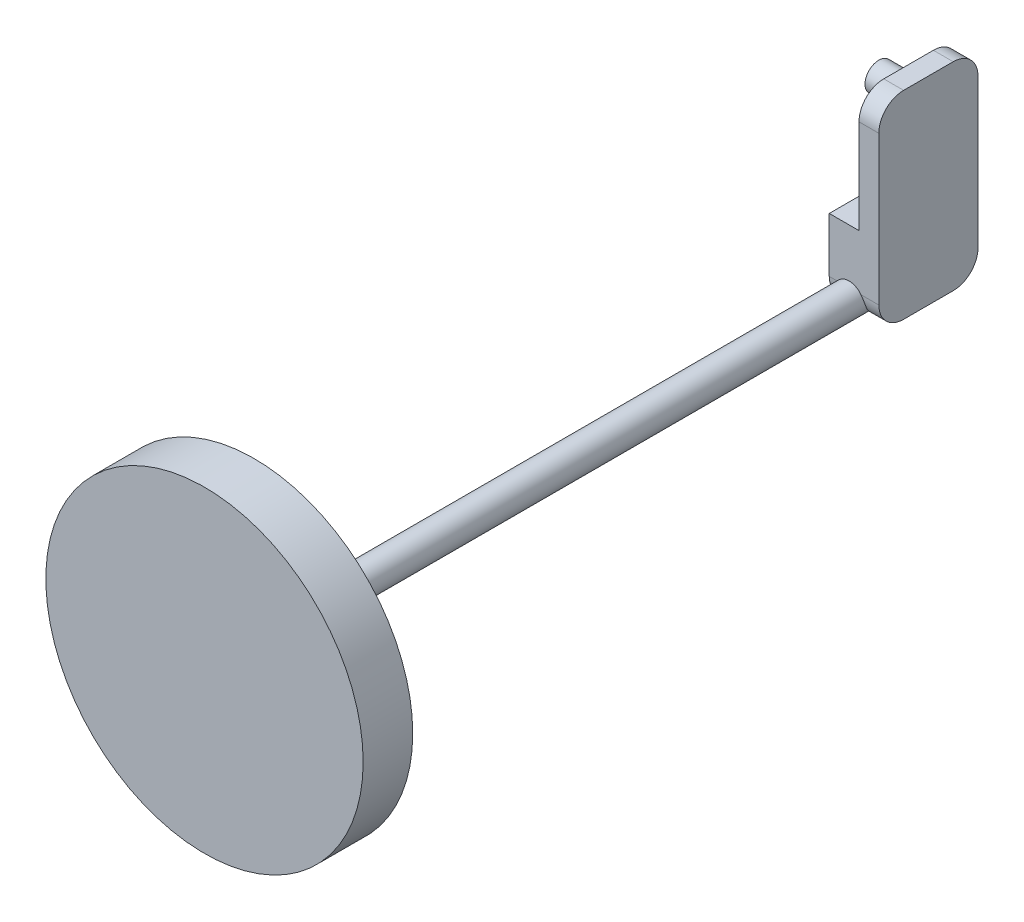
SolidWorks part; units mm, degrees
ref_plane "Front Plane" through (0, 0, 0) normal (0, 0, 1) x (1, 0, 0)
ref_plane "Top Plane" through (0, 0, 0) normal (0, 1, 0) x (1, 0, 0)
ref_plane "Right Plane" through (0, 0, 0) normal (1, 0, 0) x (0, 0, -1)
sketch "Sketch1" plane through (0, 0, 0) normal (0, 0, 1) x (1, 0, 0)
  circle A0 centre (0, 0) radius 400
  dimension "D1" = 800
extrude "Boss-Extrude1" add sketch "Sketch1" along normal blind 125
sketch "Sketch2" plane through (0, 0, 0) normal (0, 0, -1) x (-1, 0, 0)
  circle A0 centre (0, 0) radius 37.5
  dimension "D1" = 75
extrude "Boss-Extrude2" add sketch "Sketch2" along normal blind 1500
sketch "Sketch3" plane through (0, 0, -1500) normal (0, 0, -1) x (-1, 0, 0)
  line L1 (-25, 460) -> (-75, 460)
  line L2 (-25, 460) -> (-25, -40)
  line L3 (-25, -40) -> (-75, -40)
  line L4 (-75, 460) -> (-75, -40)
  dimension "D1" = 500
  dimension "D2" = 50
  dimension "D3" = 460
  dimension "D4" = 25
extrude "Boss-Extrude3" add sketch "Sketch3" along normal blind 250
sketch "Sketch4" plane through (25, 0, 0) normal (-1, 0, 0) x (0, 0, 1)
  line L0 (-1500, 27.9508) -> (-1500, 460) construction
  line L1 (-1500, -40) -> (-1625, -40)
  line L2 (-1500, -40) -> (-1500, 160)
  line L3 (-1500, 160) -> (-1625, 160)
  line L4 (-1625, -40) -> (-1625, 160)
  line L5 (-1750, -40) -> (-1500, -40) construction
  circle A0 centre (-1687.5, 60) radius 18.75
  circle A1 centre (-1625, 397.09) radius 35
  dimension "D5" = 37.5
  dimension "D6" = 70
  dimension "D1" = 125
  dimension "D2" = 200
  dimension "D3" = 62.5
  dimension "D4" = 100
  dimension "D7" = 397.09
extrude "Boss-Extrude4" add sketch "Sketch4" along normal blind 75
fillet "Fillet1" radius 62.5 4 edges at (12.5, -40, -1500) (50, -40, -1750) (50, 460, -1750) (50, 460, -1500)
